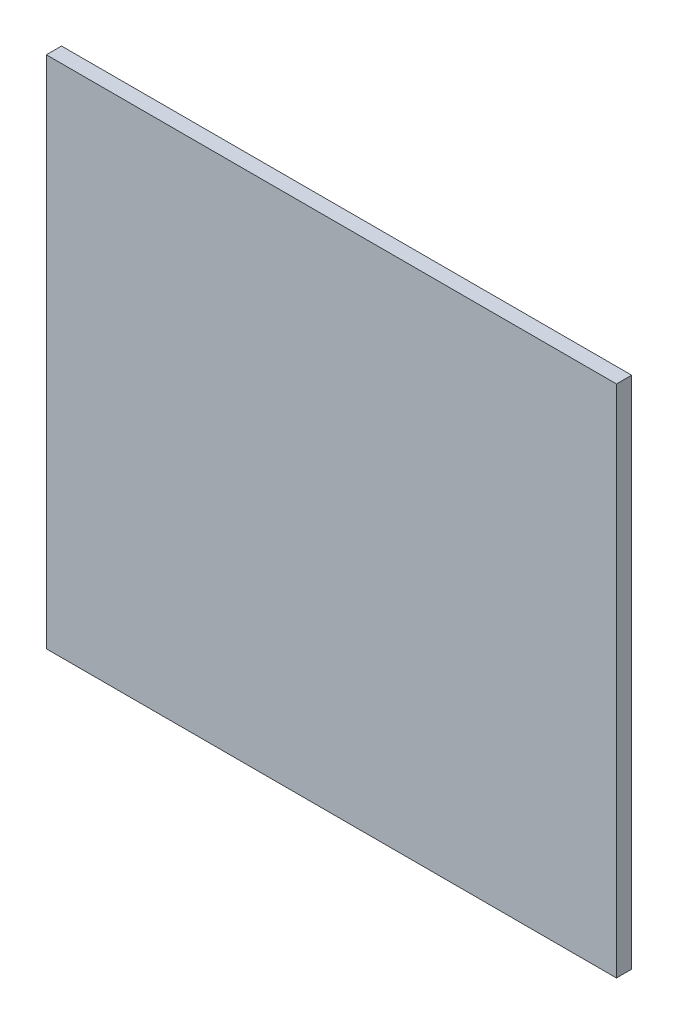
SolidWorks part; units mm, degrees
ref_plane "Front Plane" through (0, 0, 0) normal (0, 0, 1) x (1, 0, 0)
ref_plane "Top Plane" through (0, 0, 0) normal (0, 1, 0) x (1, 0, 0)
ref_plane "Right Plane" through (0, 0, 0) normal (1, 0, 0) x (0, 0, -1)
sketch "Sketch1" plane through (0, 0, 0) normal (0, 0, 1) x (1, 0, 0)
  line L1 (-169, -152.5) -> (169, -152.5)
  line L2 (-169, -152.5) -> (-169, 152.5)
  line L3 (-169, 152.5) -> (169, 152.5)
  line L4 (169, -152.5) -> (169, 152.5)
  line L5 (-169, -152.5) -> (169, 152.5) construction
  line L6 (-169, 152.5) -> (169, -152.5) construction
  point P0 (0, 0)
  dimension "D1" = 338
  dimension "D2" = 305
extrude "Boss-Extrude1" add sketch "Sketch1" along normal blind 9
equation "\"PCLength\"= 320mm'Length across I/O from PS to GPU"
equation "\"PCWidth\"= 242mm'Distance of longest part parallel to GPU(ussually GPU)"
equation "\"PCHeight\"= 172mm'Tallest point with mobo laying flat"
equation "\"WallThickness\"= 9mm'Thickness of each outer tank wall"
equation "\"ThermoBarrierThickness\"= 3mm'Thickness of barrier between hot side and cold side"
equation "\"HotSideGap\"= 25mm'Space in the hot side for a pump"
equation "\"PCClearance\"= 30mm'Clearance from top of tank to top of PC"
equation "\"RadiatorHeight\"= 275mm'Final Height from ground of radiators"
equation "\"D1@Sketch1\"=\"PCLength\" + (2 * \"WallThickness\")"
equation "\"D2@Sketch1\"=\"RadiatorHeight\" + \"PCClearance\""
equation "\"D1@Boss-Extrude1\"=\"WallThickness\""
